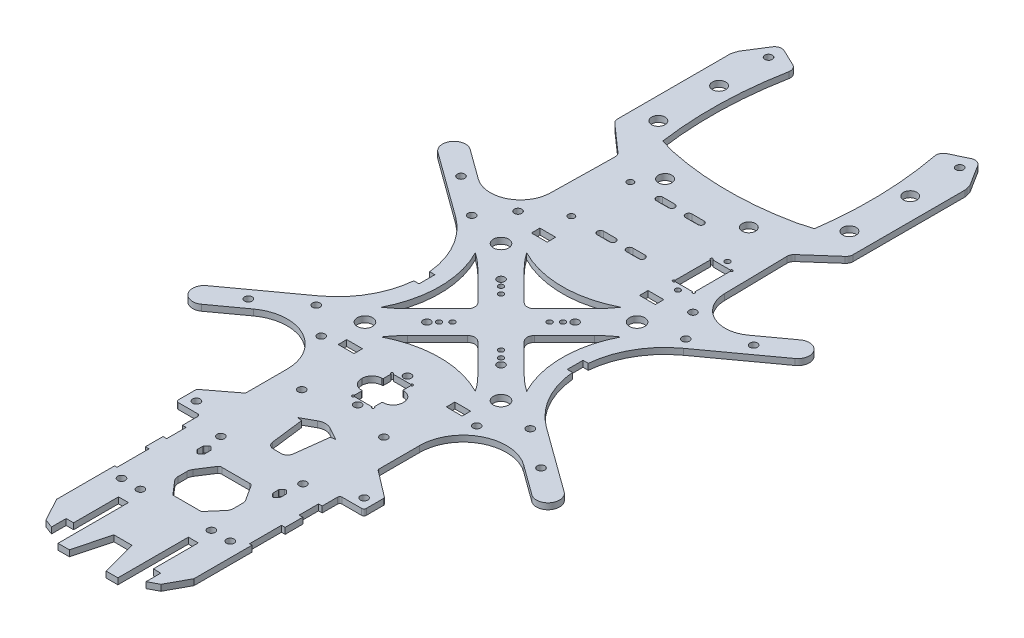
SolidWorks part; units mm, degrees
material "PPS"
ref_plane "前视基准面" through (0, 0, 0) normal (0, 0, 1) x (1, 0, 0)
ref_plane "上视基准面" through (0, 0, 0) normal (0, 1, 0) x (1, 0, 0)
ref_plane "右视基准面" through (0, 0, 0) normal (1, 0, 0) x (0, 0, -1)
sketch "草图1" plane through (0, 0, 0) normal (0, 1, 0) x (1, 0, 0)
  line L0 (-126.4995, 0) -> (116.8967, 0) construction
  line L1 (121.619, 121.619) -> (-121.619, -121.619) construction
  line L2 (0, 104.5414) -> (0, -99.6328) construction
  line L3 (-108.3893, 108.3893) -> (124.9236, -124.9236) construction
  line L4 (0, 0) -> (86.3378, -62.728) construction
  line L5 (21.4, 65.75) -> (28.6, 65.75)
  line L6 (20.9, 50.75) -> (20.9, 65.25)
  line L19 (21.4, 50.25) -> (28.6, 50.25)
  line L20 (35.3841, 83.6272) -> (48.4165, 95.1336)
  line L21 (0, 82.79) -> (0, 88.225) construction
  line L22 (17.0991, -107.7737) -> (17.0991, -105.6162)
  line L23 (-25.2781, 96.1111) -> (-31.2329, 97.7907)
  line L25 (27.2573, -95.1) -> (28.7573, -95.1) construction
  line L28 (15.9026, -104.2126) -> (16.9526, -105.2626)
  line L29 (14.1455, -105.2626) -> (15.1955, -104.2126)
  line L30 (-16.9545, -108.1273) -> (-15.9045, -109.1773)
  line L35 (73.5338, -47.5541) -> (46.853, -28.1694)
  line L36 (-15.1974, -109.1773) -> (-14.1474, -108.1273)
  line L37 (-14.0009, -105.6162) -> (-14.0009, -107.7737)
  line L38 (-14.1474, -105.2626) -> (-15.1974, -104.2126)
  line L39 (-48.4165, 95.1336) -> (-48.4165, 143.0516)
  line L40 (-35.3841, 83.6272) -> (-48.4165, 95.1336)
  line L42 (28.7573, -95.1) -> (28.7573, -102.35)
  line L59 (0, 72.0242) -> (0, 60.8242) construction
  line L64 (20.9, 58) -> (32.4846, 58) construction
  line L65 (25, 65.75) -> (25, 50.25) construction
  line L66 (29.1, 65.25) -> (29.1, 50.75)
  line L69 (-28.3, 64.3716) -> (-2.5276, 64.3716) construction
  line L72 (28.7573, -102.35) -> (27.2573, -102.35)
  line L80 (-15.9045, -104.2126) -> (-16.9545, -105.2626)
  line L81 (-17.1009, -107.7737) -> (-17.1009, -105.6162)
  line L82 (4.1009, -56.25) -> (4.1009, -53.2975)
  line L83 (-3.6009, -56.75) -> (3.6009, -56.75)
  line L84 (3.6009, -40.75) -> (-3.5991, -40.75)
  line L85 (4.1009, -41.25) -> (4.1009, -44.2025)
  line L86 (-4.1009, -56.25) -> (-4.1009, -53.2961)
  line L87 (-4.1009, -44.2011) -> (-4.1009, -41.2481)
  line L88 (-4.5484, -52.9461) -> (-4.4509, -52.9461)
  line L89 (-8.5484, -48.9461) -> (-8.5484, -48.5511)
  line L90 (8.5484, -48.9475) -> (8.5484, -48.5525)
  line L91 (4.4509, -52.9475) -> (4.5484, -52.9475)
  line L92 (4.5484, -44.5525) -> (4.4509, -44.5525)
  line L93 (-4.5484, -44.5511) -> (-4.4509, -44.5511)
  line L94 (13.9991, -105.6162) -> (13.9991, -107.7737)
  line L95 (15.1955, -109.1773) -> (14.1455, -108.1273)
  line L96 (16.9526, -108.1273) -> (15.9026, -109.1773)
  line L97 (18.9991, -62.5) -> (18.9991, -100.5) construction
  line L98 (18.9991, -100.5) -> (-19.0009, -100.5) construction
  line L99 (-19.0009, -62.5) -> (-19.0009, -100.5) construction
  line L100 (27.2573, -102.35) -> (27.2573, -110.35)
  line L101 (16.4174, -141.0041) -> (16.4174, -159.5041)
  line L102 (16.4174, -141.0041) -> (12.3174, -141.0041)
  line L103 (12.3174, -141.0041) -> (12.3174, -170.0041)
  line L104 (19.4666, -159.5041) -> (16.4174, -159.5041)
  line L105 (19.4666, -165.5542) -> (19.4666, -159.5041)
  line L106 (-3.8169, -155.5041) -> (-7.6919, -170.0041)
  line L107 (-7.6919, -170.0041) -> (-12.3174, -170.0041)
  line L108 (23.4926, -163.4505) -> (19.4666, -165.5542)
  line L109 (-19.4666, -165.5542) -> (-19.4666, -159.5041)
  line L110 (-19.4666, -159.5041) -> (-16.4174, -159.5041)
  line L111 (-12.3174, -141.0041) -> (-12.3174, -170.0041)
  line L112 (-16.4174, -141.0041) -> (-12.3174, -141.0041)
  line L113 (-16.4174, -141.0041) -> (-16.4174, -159.5041)
  line L114 (7.4592, -170.0041) -> (12.3174, -170.0041)
  line L115 (-3.8169, -155.5041) -> (3.6009, -155.5041)
  line L116 (3.6009, -155.5041) -> (7.4592, -170.0041)
  line L117 (-23.1028, -164.168) -> (-19.4666, -165.5542)
  line L118 (-10.8641, -115.9341) -> (-6.9283, -109.8213)
  line L119 (-10.5808, -123.7337) -> (-5.8541, -129.2069)
  line L120 (-5.8541, -129.2069) -> (5.8541, -129.2069)
  line L121 (-11.4015, -121.5278) -> (-11.4015, -117.7612)
  line L122 (27.2573, -110.35) -> (28.7573, -110.35)
  line L123 (28.2798, -130.7335) -> (28.2798, -154.6401)
  line L124 (28.2798, -154.6401) -> (23.4926, -163.4505)
  line L125 (-28.2798, -154.6401) -> (-23.1028, -164.168)
  line L126 (-28.2798, -130.7335) -> (-28.2798, -154.6401)
  line L127 (28.7573, -110.35) -> (28.7573, -117.6)
  line L128 (28.7573, -117.6) -> (27.2573, -117.6)
  line L129 (27.2573, -117.6) -> (27.2573, -130.7962)
  line L130 (27.2573, -130.7962) -> (28.2798, -130.7335)
  line L132 (-27.2573, -130.7962) -> (-28.2798, -130.7335)
  line L133 (-27.2573, -117.6) -> (-27.2573, -130.7962)
  line L134 (-28.7573, -117.6) -> (-27.2573, -117.6)
  line L135 (-28.7573, -110.35) -> (-28.7573, -117.6)
  line L136 (-27.2573, -110.35) -> (-28.7573, -110.35)
  line L137 (-27.2573, -102.35) -> (-27.2573, -110.35)
  line L138 (-28.7573, -102.35) -> (-27.2573, -102.35)
  line L139 (-28.7573, -95.1) -> (-28.7573, -102.35)
  line L140 (-27.2573, -95.1) -> (-28.7573, -95.1) construction
  line L142 (-73.5338, 47.5541) -> (-46.853, 28.1694)
  line L143 (-73.5338, -47.5541) -> (-46.853, -28.1694)
  line L149 (48.4165, 95.1336) -> (48.4165, 143.0516)
  line L150 (0, -114.8485) -> (0, -146.3095) construction
  line L151 (-5.6802, -109.2069) -> (5.6802, -109.2069)
  line L152 (10.5808, -123.7337) -> (5.8541, -129.2069)
  line L153 (11.4015, -121.5278) -> (11.4015, -117.7612)
  line L154 (10.8641, -115.9341) -> (6.9283, -109.8213)
  line L155 (-19.0009, -62.5) -> (18.9991, -62.5) construction
  line L166 (-11.2799, 76.5216) -> (-6.2799, 76.5216) construction
  line L169 (-11.2799, 77.8216) -> (-6.2799, 77.8216)
  line L170 (-11.2799, 75.2216) -> (-6.2799, 75.2216)
  line L171 (-11.2799, 52.2216) -> (-6.2799, 52.2216) construction
  line L172 (-11.2799, 50.9216) -> (-6.2799, 50.9216)
  line L173 (-11.2799, 53.5216) -> (-6.2799, 53.5216)
  line L174 (5.7201, 76.5216) -> (0.7201, 76.5216) construction
  line L175 (5.7201, 75.2216) -> (0.7201, 75.2216)
  line L176 (5.7201, 77.8216) -> (0.7201, 77.8216)
  line L177 (5.7201, 52.2216) -> (0.7201, 52.2216) construction
  line L178 (5.7201, 53.5216) -> (0.7201, 53.5216)
  line L179 (5.7201, 50.9216) -> (0.7201, 50.9216)
  line L180 (73.5338, 47.5541) -> (46.853, 28.1694)
  line L181 (44.0442, 32) -> (60.2246, 43.7557) construction
  line L183 (25.2781, 96.1111) -> (31.2329, 97.7907)
  line L184 (47.6512, 145.4189) -> (48.4165, 143.0516)
  line L188 (-47.6512, 145.4189) -> (-40.8875, 156.1591)
  line L190 (47.6512, 145.4189) -> (40.8875, 156.1591)
  line L192 (31.6811, 151.7709) -> (40.8875, 156.1591)
  line L193 (-40.8875, 156.1591) -> (-31.6811, 151.7709)
  line L194 (-47.6512, 145.4189) -> (-48.4165, 143.0516)
  line L195 (67.9498, 55.2397) -> (55.6247, 46.285)
  line L196 (35.3841, 83.6272) -> (35.8675, 56.1341)
  line L197 (-35.3841, 83.6272) -> (-35.8675, 56.1341)
  line L198 (-67.9498, 55.2397) -> (-55.6247, 46.285)
  line L199 (55.6018, -46.2684) -> (67.9498, -55.2397)
  line L200 (27.2573, -60.7106) -> (27.2573, -95.1) construction
  line L201 (-27.2573, -60.7106) -> (-27.2573, -95.1) construction
  line L202 (-55.6018, -46.2684) -> (-67.9498, -55.2397)
  line L203 (28.7573, -95.1) -> (38.6804, -95.1)
  line L204 (38.6804, -95.1) -> (38.6804, -86.6)
  line L205 (38.6804, -86.6) -> (27.2573, -77.9053)
  line L206 (27.2573, -60.7106) -> (27.2573, -77.9053)
  line L207 (-38.6804, -86.6) -> (-27.2573, -77.9053)
  line L208 (-38.6804, -95.1) -> (-38.6804, -86.6)
  line L209 (-28.7573, -95.1) -> (-38.6804, -95.1)
  line L210 (-27.2573, -60.7106) -> (-27.2573, -77.9053)
  circle A0 centre (10, 10) radius 1.075
  circle A1 centre (12.75, 12.75) radius 1.075
  circle A2 centre (15.25, 15.25) radius 1.55
  circle A3 centre (-15.25, 15.25) radius 1.55
  circle A4 centre (-12.75, 12.75) radius 1.075
  circle A5 centre (-10, 10) radius 1.075
  circle A6 centre (-10, -10) radius 1.075
  circle A7 centre (-12.75, -12.75) radius 1.075
  circle A8 centre (-15.25, -15.25) radius 1.55
  circle A9 centre (15.25, -15.25) radius 1.55
  circle A10 centre (12.75, -12.75) radius 1.075
  circle A11 centre (10, -10) radius 1.075
  circle A14 centre (28, -28) radius 3.15
  circle A15 centre (-28, -28) radius 3.15
  circle A16 centre (25, 68.2) radius 1.05
  arc A17 (20.9, 65.25) -> (21.4, 65.75) centre (20.9, 65.75) cw
  arc A18 (20.9, 50.75) -> (21.4, 50.25) centre (20.9, 50.25) ccw
  circle A31 centre (25, 47.8) radius 1.05
  circle A34 centre (17.238, 84.7633) radius 2.75
  circle A35 centre (-17.238, 84.7633) radius 2.75
  circle A36 centre (-39.335, 104.0823) radius 2.75
  circle A37 centre (-39.335, 129.0823) radius 2.75
  circle A38 centre (-28, 28) radius 3.15
  circle A39 centre (28, 28) radius 3.15
  circle A43 centre (44.0442, -32) radius 1.55
  circle A44 centre (60.2246, -43.7557) radius 1.55
  circle A47 centre (-60.2246, -43.7557) radius 1.55
  arc A63 (29.1, 65.25) -> (28.6, 65.75) centre (29.1, 65.75) ccw
  arc A64 (29.1, 50.75) -> (28.6, 50.25) centre (29.1, 50.25) cw
  circle A65 centre (-23.2799, 76.5216) radius 1.3
  circle A68 centre (-23.2799, 52.2216) radius 1.3
  circle A71 centre (-44.0442, -32) radius 1.55
  circle A72 centre (60.2246, 43.7557) radius 1.55
  circle A73 centre (44.0442, 32) radius 1.55
  circle A74 centre (-44.0442, 32) radius 1.55
  circle A75 centre (-60.2246, 43.7557) radius 1.55
  arc A76 (-11.2799, 77.8216) -> (-11.2799, 75.2216) centre (-11.2799, 76.5216) ccw
  arc A77 (67.9498, -55.2397) -> (73.5338, -47.5541) centre (70.7418, -51.3969) ccw
  arc A79 (-17.1009, -107.7737) -> (-16.9545, -108.1273) centre (-16.6009, -107.7737) ccw
  arc A80 (-15.9045, -109.1773) -> (-15.1974, -109.1773) centre (-15.5509, -108.8237) ccw
  arc A81 (-14.0009, -107.7737) -> (-14.1474, -108.1273) centre (-14.5009, -107.7737) cw
  arc A82 (-14.0009, -105.6162) -> (-14.1474, -105.2626) centre (-14.5009, -105.6162) ccw
  arc A83 (-15.1974, -104.2126) -> (-15.9045, -104.2126) centre (-15.5509, -104.5662) ccw
  arc A84 (-17.1009, -105.6162) -> (-16.9545, -105.2626) centre (-16.6009, -105.6162) cw
  arc A85 (-4.1009, -56.25) -> (-3.6009, -56.75) centre (-4.1009, -56.75) ccw
  arc A86 (4.1009, -56.25) -> (3.6009, -56.75) centre (4.1009, -56.75) cw
  arc A87 (4.1009, -41.25) -> (3.6009, -40.75) centre (4.1009, -40.75) ccw
  arc A88 (-4.1009, -41.2481) -> (-3.5991, -40.75) centre (-4.0991, -40.7481) cw
  arc A89 (8.5484, -48.5525) -> (4.5484, -44.5525) centre (4.5484, -48.5525) ccw
  arc A90 (-4.5484, -44.5511) -> (-8.5484, -48.5511) centre (-4.5484, -48.5511) ccw
  arc A91 (-4.5484, -52.9461) -> (-8.5484, -48.9461) centre (-4.5484, -48.9461) cw
  arc A92 (8.5484, -48.9475) -> (4.5484, -52.9475) centre (4.5484, -48.9475) cw
  arc A93 (4.1009, -44.2025) -> (4.4509, -44.5525) centre (4.4509, -44.2025) ccw
  arc A94 (4.1009, -53.2975) -> (4.4509, -52.9475) centre (4.4509, -53.2975) cw
  arc A95 (-4.1009, -44.2011) -> (-4.4509, -44.5511) centre (-4.4509, -44.2011) cw
  arc A96 (-4.1009, -53.2961) -> (-4.4509, -52.9461) centre (-4.4509, -53.2961) ccw
  arc A97 (17.0991, -107.7737) -> (16.9526, -108.1273) centre (16.5991, -107.7737) cw
  arc A98 (17.0991, -105.6162) -> (16.9526, -105.2626) centre (16.5991, -105.6162) ccw
  arc A99 (15.1955, -104.2126) -> (15.9026, -104.2126) centre (15.5491, -104.5662) cw
  arc A100 (13.9991, -105.6162) -> (14.1455, -105.2626) centre (14.4991, -105.6162) cw
  arc A101 (13.9991, -107.7737) -> (14.1455, -108.1273) centre (14.4991, -107.7737) ccw
  arc A102 (15.9026, -109.1773) -> (15.1955, -109.1773) centre (15.5491, -108.8237) cw
  circle A103 centre (-22.3899, -133.8062) radius 1.55
  circle A104 centre (22.3899, -133.8062) radius 1.55
  circle A105 centre (-16.9009, -98.4) radius 1.55
  circle A106 centre (16.8991, -98.4) radius 1.55
  arc A107 (-5.6802, -109.2069) -> (-6.9283, -109.8213) centre (-5.7932, -110.5521) ccw
  arc A108 (-11.4015, -117.7612) -> (-10.8641, -115.9341) centre (-8.0265, -117.7612) cw
  arc A109 (-10.5808, -123.7337) -> (-11.4015, -121.5278) centre (-8.0265, -121.5278) cw
  circle A110 centre (-14.6009, -133.8062) radius 1.55
  circle A111 centre (14.6009, -133.8062) radius 1.55
  arc A112 (10.5808, -123.7337) -> (11.4015, -121.5278) centre (8.0265, -121.5278) ccw
  arc A113 (11.4015, -117.7612) -> (10.8641, -115.9341) centre (8.0265, -117.7612) ccw
  arc A114 (5.6802, -109.2069) -> (6.9283, -109.8213) centre (5.7932, -110.5521) cw
  arc A132 (-6.2799, 75.2216) -> (-6.2799, 77.8216) centre (-6.2799, 76.5216) ccw
  arc A133 (-11.2799, 50.9216) -> (-11.2799, 53.5216) centre (-11.2799, 52.2216) cw
  arc A134 (-6.2799, 53.5216) -> (-6.2799, 50.9216) centre (-6.2799, 52.2216) cw
  arc A135 (5.7201, 75.2216) -> (5.7201, 77.8216) centre (5.7201, 76.5216) ccw
  arc A136 (0.7201, 77.8216) -> (0.7201, 75.2216) centre (0.7201, 76.5216) ccw
  arc A137 (5.7201, 53.5216) -> (5.7201, 50.9216) centre (5.7201, 52.2216) cw
  arc A138 (0.7201, 50.9216) -> (0.7201, 53.5216) centre (0.7201, 52.2216) cw
  circle A143 centre (-16.9009, -65.108) radius 1.55
  circle A144 centre (16.9009, -65.108) radius 1.55
  circle A145 centre (0, -38.5) radius 1.55
  circle A146 centre (0, -59) radius 1.55
  arc A147 (67.9498, 55.2397) -> (73.5338, 47.5541) centre (70.7418, 51.3969) cw
  arc A148 (46.853, 28.1694) -> (46.853, -28.1694) centre (67.3193, 0) ccw
  circle A149 centre (44.0442, -32) radius 6 construction
  arc A151 (-67.9498, 55.2397) -> (-73.5338, 47.5541) centre (-70.7418, 51.3969) ccw
  arc A153 (-46.853, 28.1694) -> (-46.853, -28.1694) centre (-67.3193, 0) cw
  arc A154 (-67.9498, -55.2397) -> (-73.5338, -47.5541) centre (-70.7418, -51.3969) cw
  circle A158 centre (39.335, 129.0823) radius 2.75
  circle A159 centre (39.335, 104.0823) radius 2.75
  arc A160 (-25.2781, 96.1111) -> (25.2781, 96.1111) centre (0, 215.2587) ccw
  circle A161 centre (-36, 43) radius 1.55
  circle A164 centre (36, 43) radius 1.55
  circle A165 centre (-32, -42) radius 1.55
  circle A166 centre (32, -42) radius 1.55
  circle A171 centre (-39.335, 149.4323) radius 1.55
  arc A176 (30.0249, 148.5011) -> (31.6811, 151.7709) centre (32.9719, 149.0628) cw
  arc A178 (30.0249, 148.5011) -> (31.2329, 97.7907) centre (-122.0773, 119.5082) cw
  arc A180 (-30.0249, 148.5011) -> (-31.2329, 97.7907) centre (122.0773, 119.5082) ccw
  arc A181 (-31.6811, 151.7709) -> (-30.0249, 148.5011) centre (-32.9719, 149.0628) cw
  arc A182 (55.6247, 46.285) -> (35.8675, 56.1341) centre (48.31, 56.3528) cw
  arc A183 (-55.6247, 46.285) -> (-35.8675, 56.1341) centre (-48.31, 56.3528) ccw
  circle A185 centre (39.335, 149.4323) radius 1.55
  arc A186 (55.6018, -46.2684) -> (27.2573, -60.7106) centre (45.1089, -60.7106) ccw
  arc A187 (-55.6018, -46.2684) -> (-27.2573, -60.7106) centre (-45.1089, -60.7106) cw
  circle A188 centre (34.5, -90.85) radius 1.55
  circle A189 centre (-34.5, -90.85) radius 1.55
  point P47 (-8.7799, 76.5216)
  point P104 (-32.5, 0)
  point P105 (32.5, 0)
  point P110 (3.2201, 76.5216)
  point P115 (-8.7799, 52.2216)
  point P171 (3.2201, 52.2216)
  point P214 (38.6804, -90.85)
  point P354 (0, -129.2069)
  point P361 (7.3036, -118.1341)
  point P364 (0, -109.2069)
  dimension "D2" = 2.15
  dimension "D5" = 3.1
  dimension "D7" = 3.1
  dimension "D8" = 36
  dimension "D10" = 0.5
  dimension "D11" = 3.1
  dimension "D20" = 2.6
  dimension "D22" = 3.1
  dimension "D32" = 7.25
  dimension "D12" = 12
  dimension "D15" = 12
  dimension "D13" = 5
  dimension "D9" = 3.1
  dimension "D25" = 4.75
  dimension "D26" = 13
  dimension "D31" = 12
  dimension "D41" = 96.833
  dimension "D49" = 32
  dimension "D54" = 45.35
  dimension "D59" = 8.5
  dimension "D3" = 10
  dimension "D4" = 2.75
  dimension "D6" = 2.5
  dimension "D14" = 58
  dimension "D16" = 2.608
  dimension "D17" = 15.5
  dimension "D18" = 2.45
  dimension "D19" = 8.2
  dimension "D21" = 24.3
  dimension "D23" = 2.25
  dimension "D24" = 2.25
  dimension "D27" = 20
  dimension "D28" = 25
  dimension "D29" = 25
  dimension "D30" = 32
  dimension "D33" = 1.5
  dimension "D34" = 2.1
  dimension "D35" = 10.5
  dimension "D36" = 14.5
  dimension "D37" = 4
  dimension "D38" = 4.1
  dimension "D39" = 8
  dimension "D40" = 65
  dimension "D42" = 70.7683
  dimension "D43" = 43
  dimension "D44" = 20
  dimension "D45" = 40.75
  dimension "D46" = 7.2
  dimension "D47" = 16
  dimension "D48" = 62.5
  dimension "D50" = 38
  dimension "D51" = 7.2
  dimension "D52" = 36
  dimension "D53" = 42
  dimension "D55" = 90.85
  dimension "D56" = 83.6272
  dimension "D57" = 11.5064
  dimension "D58" = 34.5
extrude "凸台-拉伸1" add sketch "草图1" along normal blind 2.5
sketch "草图6" plane through (0, 2.5, 0) normal (0, 1, 0) x (1, 0, 0)
  line L1 (-23.978, 14.4296) -> (-9.5485, 0)
  line L2 (-126.4995, 0) -> (116.8967, 0) construction
  line L3 (-58.8867, 0) -> (57.6096, 0) construction
  line L4 (-23.978, -14.4296) -> (-9.5485, 0)
  line L5 (0, 29.8455) -> (0, -115.5328) construction
  line L6 (0, 104.5414) -> (0, -99.6328) construction
  line L14 (14.4296, 23.978) -> (0, 9.5485)
  line L15 (-14.4296, 23.978) -> (0, 9.5485)
  line L20 (2.5276, -72.9435) -> (7.8986, -75.8938)
  line L21 (-7.8986, -75.8938) -> (-2.5276, -72.9435)
  line L22 (-1.6288, -92.0995) -> (1.6288, -92.0995)
  line L23 (-5.924, -76.1216) -> (-4.2339, -89.7964)
  line L24 (5.924, -76.1216) -> (4.2339, -89.7964)
  line L25 (-7.8986, -75.8938) -> (-5.924, -76.1216)
  line L26 (7.8986, -75.8938) -> (5.924, -76.1216)
  line L27 (23.978, -14.4296) -> (9.5485, 0)
  line L28 (23.978, 14.4296) -> (9.5485, 0)
  line L29 (-14.4296, -23.978) -> (0, -9.5485)
  line L30 (14.4296, -23.978) -> (0, -9.5485)
  arc A3 (-23.978, 14.4296) -> (-29.9602, 19.3706) centre (-52.8883, -14.4807) ccw
  arc A5 (-23.978, -14.4296) -> (-29.9602, -19.3706) centre (-52.8883, 14.4807) cw
  arc A6 (-29.9602, -19.3706) -> (-29.9602, 19.3706) centre (-67.3193, 0) ccw
  arc A18 (-14.4296, 23.978) -> (-19.3706, 29.9602) centre (14.4807, 52.8883) cw
  arc A19 (-19.3706, 29.9602) -> (19.3706, 29.9602) centre (0, 67.3193) ccw
  arc A20 (14.4296, 23.978) -> (19.3706, 29.9602) centre (-14.4807, 52.8883) ccw
  arc A27 (2.5276, -72.9435) -> (-2.5276, -72.9435) centre (0, -77.545) ccw
  arc A28 (1.6288, -92.0995) -> (4.2339, -89.7964) centre (1.6288, -89.4745) ccw
  arc A29 (-1.6288, -92.0995) -> (-4.2339, -89.7964) centre (-1.6288, -89.4745) cw
  arc A30 (23.978, 14.4296) -> (29.9602, 19.3706) centre (52.8883, -14.4807) cw
  arc A31 (29.9602, 19.3706) -> (29.9602, -19.3706) centre (67.3193, 0) ccw
  arc A32 (23.978, -14.4296) -> (29.9602, -19.3706) centre (52.8883, 14.4807) ccw
  arc A33 (14.4296, -23.978) -> (19.3706, -29.9602) centre (-14.4807, -52.8883) cw
  arc A34 (19.3706, -29.9602) -> (-19.3706, -29.9602) centre (0, -67.3193) ccw
  arc A35 (-14.4296, -23.978) -> (-19.3706, -29.9602) centre (14.4807, -52.8883) ccw
  dimension "D1" = 45
  dimension "D2" = 4
extrude "减重" cut sketch "草图6" against normal up to next
fillet "圆角1" radius 3 14 edges at (-25.2781, 1.25, -96.1111) (25.2781, 1.25, -96.1111) (48.4165, 1.25, -95.1336) (-48.4165, 1.25, -95.1336) (-9.5485, 1.25, 0) (9.5485, 1.25, 0) (0, 1.25, -9.5485) (0, 1.25, 9.5485) (48.4165, 1.25, -143.0516) (40.8875, 1.25, -156.1591) (-48.4165, 1.25, -143.0516) (-40.8875, 1.25, -156.1591) (-35.3841, 1.25, -83.6272) (35.3841, 1.25, -83.6272)
sketch "草图7" plane through (0, 2.5, 0) normal (0, 1, 0) x (1, 0, 0)
  line L0 (-81.2345, 0) -> (102.1666, 0) construction
  line L1 (0, 63.5408) -> (0, -83.9036) construction
  line L2 (34, -3.25) -> (30.5, -3.25)
  line L3 (-34, 3.25) -> (-30.5, 3.25)
  line L4 (-34, 3.25) -> (-34, -3.25)
  line L5 (-34, -3.25) -> (-30.5, -3.25)
  line L6 (-30.5, 3.25) -> (-30.5, -3.25)
  line L7 (30.5, 3.25) -> (30.5, -3.25)
  line L8 (34, 3.25) -> (30.5, 3.25)
  line L9 (34, 3.25) -> (34, -3.25)
  line L10 (19, -38) -> (25.5, -38)
  line L11 (-25.5, 41.5) -> (-19, 41.5)
  line L12 (-25.5, 41.5) -> (-25.5, 38)
  line L13 (-25.5, 38) -> (-19, 38)
  line L14 (-19, 41.5) -> (-19, 38)
  line L15 (19, -38) -> (19, -41.5)
  line L16 (19, -41.5) -> (25.5, -41.5)
  line L17 (25.5, -38) -> (25.5, -41.5)
  line L18 (-19, -38) -> (-19, -41.5)
  line L19 (-19, -41.5) -> (-25.5, -41.5)
  line L20 (-25.5, -38) -> (-25.5, -41.5)
  line L21 (-19, -38) -> (-25.5, -38)
  line L22 (25.5, 38) -> (19, 38)
  line L23 (19, 41.5) -> (19, 38)
  line L24 (25.5, 41.5) -> (19, 41.5)
  line L25 (25.5, 41.5) -> (25.5, 38)
  point P26 (19, -39.75)
  dimension "D1" = 3.5
  dimension "D2" = 6.5
  dimension "D3" = 30.5
  dimension "D4" = 38
  dimension "D5" = 19
  dimension "D6" = 38
extrude "保护壳固定点" cut sketch "草图7" against normal up to next
fillet "圆角2" radius 1 8 edges at (-28.7573, 1.25, 95.1) (-38.6804, 1.25, 95.1) (-38.6804, 1.25, 86.6) (-27.2573, 1.25, 77.9053) (27.2573, 1.25, 77.9053) (38.6804, 1.25, 86.6) (38.6804, 1.25, 95.1) (28.7573, 1.25, 95.1)
